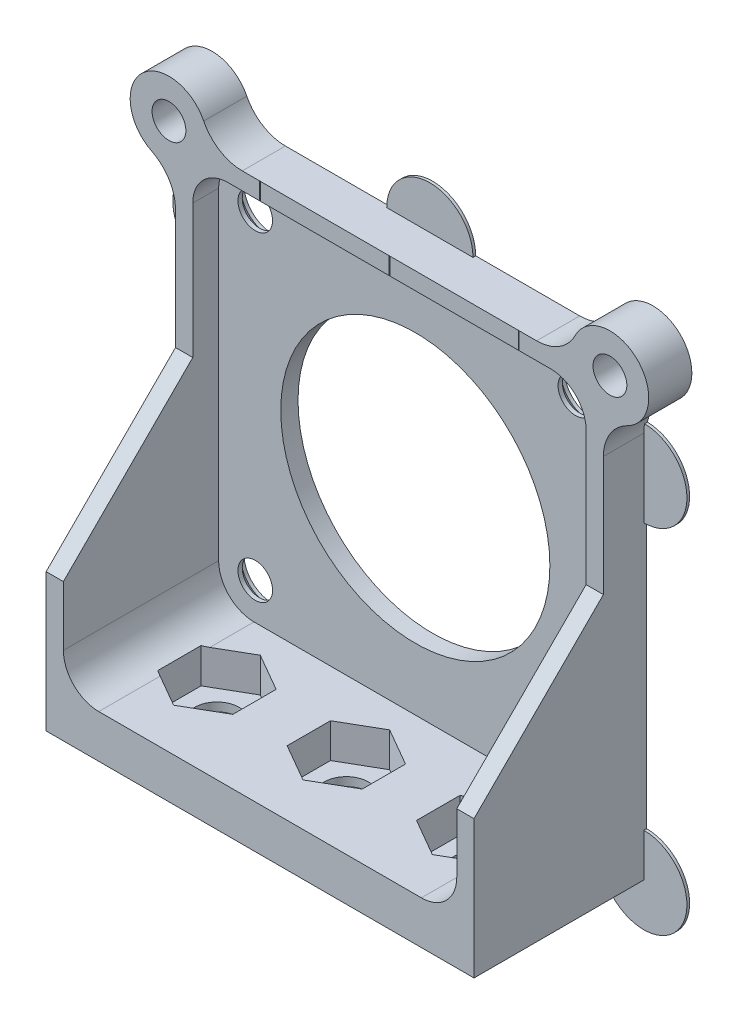
SolidWorks part; units mm, degrees
ref_plane "Front Plane" through (0, 0, 0) normal (0, 0, 1) x (1, 0, 0)
ref_plane "Top Plane" through (0, 0, 0) normal (0, 1, 0) x (1, 0, 0)
ref_plane "Right Plane" through (0, 0, 0) normal (1, 0, 0) x (0, 0, -1)
sketch "Sketch2" plane through (0, 0, 0) normal (0, 0, 1) x (1, 0, 0)
  line L12 (-28.2, 23.755) -> (-28.2, -23.755)
  line L13 (-23.755, -28.2) -> (23.755, -28.2)
  line L14 (28.2, -23.755) -> (28.2, 23.755)
  line L15 (23.755, 28.2) -> (-23.755, 28.2)
  circle A0 centre (0, 0) radius 19.05
  circle A1 centre (-23.57, 23.57) radius 2.55
  circle A2 centre (23.57, 23.57) radius 2.55
  circle A3 centre (23.57, -23.57) radius 2.55
  circle A4 centre (-23.57, -23.57) radius 2.55
  arc A12 (-23.755, 28.2) -> (-28.2, 23.755) centre (-23.755, 23.755) ccw
  arc A13 (-28.2, -23.755) -> (-23.755, -28.2) centre (-23.755, -23.755) ccw
  arc A14 (23.755, -28.2) -> (28.2, -23.755) centre (23.755, -23.755) ccw
  arc A15 (28.2, 23.755) -> (23.755, 28.2) centre (23.755, 23.755) ccw
sketch "Sketch3" plane through (0, 0, 0) normal (0, 0, 1) x (1, 0, 0)
  line L9 (23.755, 31.502) -> (-23.755, 31.502)
  line L10 (-31.502, 23.755) -> (-31.502, -23.755)
  line L11 (-23.755, -31.502) -> (23.755, -31.502)
  line L12 (31.502, -23.755) -> (31.502, 23.755)
  line L13 (23.755, 28.962) -> (-23.755, 28.962)
  line L14 (-28.962, 23.755) -> (-28.962, -23.755)
  line L15 (-23.755, -28.962) -> (23.755, -28.962)
  line L16 (28.962, -23.755) -> (28.962, 23.755)
  line L17 (23.755, 28.962) -> (-23.755, 28.962) construction
  line L18 (-28.962, 23.755) -> (-28.962, -23.755) construction
  line L19 (-23.755, -28.962) -> (23.755, -28.962) construction
  line L20 (28.962, -23.755) -> (28.962, 23.755) construction
  circle A0 centre (0, 0) radius 19.812
  circle A1 centre (23.57, 23.57) radius 2.55
  circle A2 centre (-23.57, 23.57) radius 2.55
  circle A3 centre (-23.57, -23.57) radius 2.55
  circle A4 centre (23.57, -23.57) radius 2.55
  circle A9 centre (0, 0) radius 19.05 construction
  arc A10 (-23.755, 31.502) -> (-31.502, 23.755) centre (-23.755, 23.755) ccw
  arc A11 (-31.502, -23.755) -> (-23.755, -31.502) centre (-23.755, -23.755) ccw
  arc A12 (23.755, -31.502) -> (31.502, -23.755) centre (23.755, -23.755) ccw
  arc A13 (31.502, 23.755) -> (23.755, 31.502) centre (23.755, 23.755) ccw
  arc A14 (-23.755, 28.962) -> (-28.962, 23.755) centre (-23.755, 23.755) ccw
  arc A15 (-28.962, -23.755) -> (-23.755, -28.962) centre (-23.755, -23.755) ccw
  arc A16 (23.755, -28.962) -> (28.962, -23.755) centre (23.755, -23.755) ccw
  arc A17 (28.962, 23.755) -> (23.755, 28.962) centre (23.755, 23.755) ccw
  arc A18 (-23.755, 28.962) -> (-28.962, 23.755) centre (-23.755, 23.755) ccw construction
  arc A19 (-28.962, -23.755) -> (-23.755, -28.962) centre (-23.755, -23.755) ccw construction
  arc A20 (23.755, -28.962) -> (28.962, -23.755) centre (23.755, -23.755) ccw construction
  arc A21 (28.962, 23.755) -> (23.755, 28.962) centre (23.755, 23.755) ccw construction
  dimension "D6" = 0.762
  dimension "D1" = 0.762
  dimension "D2" = 2.54
extrude "Boss-Extrude1" add sketch "Sketch3" along normal blind 2.54
sketch "Sketch16" plane through (0, 0, 2.54) normal (0, 0, 1) x (1, 0, 0)
  line L8 (23.755, 28.962) -> (-23.755, 28.962)
  line L9 (-28.962, 23.755) -> (-28.962, -23.755)
  line L10 (23.755, 31.502) -> (-23.755, 31.502)
  line L11 (-31.502, 23.755) -> (-31.502, -23.755)
  line L12 (-23.755, -31.502) -> (23.755, -31.502)
  line L13 (31.502, -23.755) -> (31.502, 23.755)
  line L14 (23.755, 31.502) -> (-23.755, 31.502)
  line L15 (-31.502, 23.755) -> (-31.502, -23.755)
  line L16 (-23.755, -31.502) -> (23.755, -31.502)
  line L17 (31.502, -23.755) -> (31.502, 23.755)
  line L18 (-23.755, -28.962) -> (23.755, -28.962)
  line L23 (28.962, -23.755) -> (28.962, 23.755)
  line L24 (23.755, 28.962) -> (-23.755, 28.962)
  line L25 (-28.962, 23.755) -> (-28.962, -23.755)
  line L26 (-23.755, -28.962) -> (23.755, -28.962)
  line L27 (28.962, -23.755) -> (28.962, 23.755)
  arc A8 (28.962, 23.755) -> (23.755, 28.962) centre (23.755, 23.755) ccw
  arc A9 (31.502, 23.755) -> (23.755, 31.502) centre (23.755, 23.755) ccw
  arc A10 (-23.755, 31.502) -> (-31.502, 23.755) centre (-23.755, 23.755) ccw
  arc A11 (-31.502, -23.755) -> (-23.755, -31.502) centre (-23.755, -23.755) ccw
  arc A12 (23.755, -31.502) -> (31.502, -23.755) centre (23.755, -23.755) ccw
  arc A13 (31.502, 23.755) -> (23.755, 31.502) centre (23.755, 23.755) ccw
  arc A14 (-23.755, 31.502) -> (-31.502, 23.755) centre (-23.755, 23.755) ccw
  arc A15 (-31.502, -23.755) -> (-23.755, -31.502) centre (-23.755, -23.755) ccw
  arc A16 (23.755, -31.502) -> (31.502, -23.755) centre (23.755, -23.755) ccw
  arc A21 (-23.755, 28.962) -> (-28.962, 23.755) centre (-23.755, 23.755) ccw
  arc A22 (-28.962, -23.755) -> (-23.755, -28.962) centre (-23.755, -23.755) ccw
  arc A23 (23.755, -28.962) -> (28.962, -23.755) centre (23.755, -23.755) ccw
  arc A24 (28.962, 23.755) -> (23.755, 28.962) centre (23.755, 23.755) ccw
  arc A25 (-23.755, 28.962) -> (-28.962, 23.755) centre (-23.755, 23.755) ccw
  arc A26 (-28.962, -23.755) -> (-23.755, -28.962) centre (-23.755, -23.755) ccw
  arc A27 (23.755, -28.962) -> (28.962, -23.755) centre (23.755, -23.755) ccw
  dimension "D1" = 0
  dimension "D2" = 2.54
extrude "Boss-Extrude6" add sketch "Sketch16" along normal blind 3.81
sketch "Sketch17" plane through (0, 0, 2.54) normal (0, 0, 1) x (1, 0, 0)
  line L0 (-31.502, 23.755) -> (-31.502, -23.755) construction
  line L1 (31.502, -35.312) -> (-31.502, -35.312)
  line L2 (31.502, -35.312) -> (31.502, -16.262)
  line L3 (31.502, -16.262) -> (28.962, -16.262)
  line L4 (-31.502, -35.312) -> (-31.502, -16.262)
  line L12 (-28.962, -16.262) -> (-31.502, -16.262)
  line L13 (-28.962, 23.755) -> (-28.962, -23.755) construction
  line L14 (28.962, -23.755) -> (28.962, 23.755) construction
  line L15 (31.502, -23.755) -> (31.502, 23.755) construction
  line L16 (-23.755, -28.962) -> (23.755, -28.962) construction
  dimension "D1" = 6.35
  dimension "D2" = 19.05
extrude "Boss-Extrude10" add sketch "Sketch17" along normal blind 22.86 and the other way blind 2.54
chamfer "Chamfer1" distance 20.32 angle 45 2 edges at (30.232, -16.262, 6.35) (-30.232, -16.262, 6.35)
sketch "Sketch18" plane through (0, -28.962, 0) normal (0, -1, 0) x (1, 0, 0)
  line L1 (0, 0) -> (0, 25.4) construction
  line L3 (19.05, 0) -> (-19.05, 0) construction
  line L4 (0, 19.0791) -> (-5.5245, 15.8896)
  line L5 (-5.5245, 15.8896) -> (-5.5245, 9.5104)
  line L6 (-5.5245, 9.5104) -> (0, 6.3209)
  line L7 (0, 6.3209) -> (5.5245, 9.5104)
  line L8 (5.5245, 9.5104) -> (5.5245, 15.8896)
  line L9 (5.5245, 15.8896) -> (0, 19.0791)
  line L13 (-31.502, 12.7) -> (31.502, 12.7) construction
  line L14 (-31.502, 25.4) -> (-31.502, 6.35) construction
  line L15 (31.502, 6.35) -> (31.502, 25.4) construction
  line L16 (-9.525, 25.4) -> (-9.525, 0) construction
  line L17 (12.452, 12.7) -> (-50.552, 12.7) construction
  line L18 (-19.05, 0) -> (-19.05, 25.4) construction
  line L19 (-24.5745, 15.8896) -> (-19.05, 19.0791)
  line L20 (-24.5745, 9.5104) -> (-24.5745, 15.8896)
  line L21 (-19.05, 6.3209) -> (-24.5745, 9.5104)
  line L22 (-13.5255, 9.5104) -> (-19.05, 6.3209)
  line L23 (-13.5255, 15.8896) -> (-13.5255, 9.5104)
  line L24 (-19.05, 19.0791) -> (-13.5255, 15.8896)
  line L25 (19.05, 0) -> (19.05, 25.4) construction
  line L26 (-12.452, 12.7) -> (50.552, 12.7) construction
  line L27 (19.05, 19.0791) -> (13.5255, 15.8896)
  line L28 (13.5255, 15.8896) -> (13.5255, 9.5104)
  line L29 (13.5255, 9.5104) -> (19.05, 6.3209)
  line L30 (19.05, 6.3209) -> (24.5745, 9.5104)
  line L31 (24.5745, 9.5104) -> (24.5745, 15.8896)
  line L32 (24.5745, 15.8896) -> (19.05, 19.0791)
  line L33 (-23.755, 25.4) -> (23.755, 25.4) construction
  circle A0 centre (0, 12.7) radius 5.5245 construction
  circle A1 centre (-19.05, 12.7) radius 5.5245 construction
  circle A2 centre (19.05, 12.7) radius 5.5245 construction
  dimension "D1" = 11.049
  dimension "D2" = 9.525
extrude "Cut-Extrude2" cut sketch "Sketch18" along normal blind 5.08 and the other way through all
hole_wizard "1/4 Clearance Hole1" positions "Sketch20" profile "Sketch19" hole size "1/4" standard "ANSI Inch" end condition through all
sketch "Sketch20" plane through (0, -34.042, 0) normal (0, 1, 0) x (1, 0, 0)
  line L4 (-24.5745, -15.8896) -> (-13.5255, -9.5104) construction
  line L5 (-19.05, -6.3209) -> (-13.5255, -9.5104) construction
  line L6 (-13.5255, -9.5104) -> (-13.5255, -15.8896) construction
  line L8 (-5.5245, -15.8896) -> (5.5245, -9.5104) construction
  line L10 (13.5255, -15.8896) -> (24.5745, -9.5104) construction
  line L12 (13.5255, -15.8896) -> (19.05, -19.0791) construction
  line L13 (19.05, -19.0791) -> (13.5255, -15.8896) construction
  point P22 (-19.05, -12.7)
  point P24 (0, -12.7)
  point P26 (19.05, -12.7)
sketch "Sketch19" plane through (-19.05, -34.042, 12.7) normal (1, 0, 0) x (0, 0, 1)
  line L0 (0, 0) -> (0, 1.27)
  line L1 (0, 1.27) -> (3.2639, 1.27)
  line L2 (3.2639, 1.27) -> (3.2639, 0)
  line L5 (3.2639, 0) -> (0, 0)
  line L11 (0, -6.35) -> (0, 107.95) construction
  dimension "Thru Hole Dia." = 6.5278
  dimension "Thru Hole Depth" = 1.27
sketch "Sketch22" plane through (0, 0, 0) normal (0, 0, -1) x (-1, 0, 0)
  line L0 (-29.233, 29.233) -> (23.57, -23.57) construction
  line L3 (-29.233, 29.233) -> (-43.8337, 43.8337) construction
  arc A0 (-23.755, 31.502) -> (-31.502, 23.755) centre (-23.755, 23.755) ccw construction
  circle A1 centre (-32.4658, 32.4658) radius 5.715
  circle A2 centre (-32.4658, 32.4658) radius 2.413
  arc A3 (-23.755, 28.2) -> (-28.2, 23.755) centre (-23.755, 23.755) ccw construction
  point P12 (-26.8981, 26.8981)
  arc M3 (-23.755, 31.502) -> (-31.502, 23.755) centre (-23.755, 23.755) ccw
  dimension "D1" = 11.43
  dimension "D2" = 4.826
  dimension "D3" = 7.874
extrude "Boss-Extrude18" add sketch "Sketch22" against normal up to surface (6.35 mm away) contours A1 A2 M3 region at (26.974, 31.6417, 0) up to face at (26.1652, 22.4046, 6.35)
mirror "Mirror3" about plane through (0, 0, 0) normal (1, 0, 0) of "Boss-Extrude18"
fillet "Fillet1" radius 6.35 4 edges at (27.0026, 30.7884, 3.175) (30.7884, 27.0026, 3.175) (-30.7884, 27.0026, 3.175) (-27.0026, 30.7884, 3.175)
hole_wizard "CSK for  Flat Head Machine Screw (100)1" positions "Sketch24" profile "Sketch23" countersink size "#10" standard "ANSI Inch" end condition through all
sketch "Sketch24" plane through (0, 0, 0) normal (0, 0, -1) x (-1, 0, 0)
  point P0 (-23.57, 23.57)
  point P3 (23.57, 23.57)
  point P6 (23.57, -23.57)
  point P9 (-23.57, -23.57)
sketch "Sketch23" plane through (23.57, 23.57, 0) normal (1, 0, 0) x (0, 1, 0)
  line L0 (0, 0) -> (0, 25.4)
  line L1 (0, 25.4) -> (2.4892, 25.4)
  line L2 (2.4892, 25.4) -> (2.4892, 1.9573)
  line L3 (2.4892, 1.9573) -> (4.2164, 0.508)
  line L4 (4.2164, 0.508) -> (4.2164, 0)
  line L6 (4.2164, 0) -> (0, 0)
  line L7 (-2.4892, 1.9573) -> (-4.2164, 0.508) construction
  line L11 (0, -6.35) -> (0, 107.95) construction
  dimension "Thru Hole Dia." = 4.9784
  dimension "Thru Hole Depth" = 25.4
  dimension "C'Sink Dia." = 8.4328
  dimension "C'Sink Angle" = 100
  dimension "Head Clearance" = 0.508
hole_wizard "#10 Clearance Hole1" positions "Sketch26" profile "Sketch25" hole size "#10" standard "ANSI Inch" end condition through all
sketch "Sketch26" plane through (0, 0, 0) normal (0, 0, -1) x (-1, 0, 0)
  point P0 (-32.4658, 32.4658)
  point P3 (32.4658, 32.4658)
sketch "Sketch25" plane through (32.4658, 32.4658, 0) normal (1, 0, 0) x (0, 1, 0)
  line L0 (0, 0) -> (0, 25.4)
  line L1 (0, 25.4) -> (2.4892, 25.4)
  line L2 (2.4892, 25.4) -> (2.4892, 0)
  line L5 (2.4892, 0) -> (0, 0)
  line L11 (0, -6.35) -> (0, 107.95) construction
  dimension "Thru Hole Dia." = 4.9784
  dimension "Thru Hole Depth" = 25.4
sketch "Sketch6" plane through (0, -30.232, 0) normal (0, 0, -1) x (-1, 0, 0)
  line L0 (0, -5.08) -> (0, 46.8212) construction
  line L1 (-31.502, -5.08) -> (31.502, -5.08) construction
  line L2 (31.502, 51.9018) -> (31.502, -5.08) construction
  line L3 (0, 20.8706) -> (31.502, 20.8706) construction
  line L4 (31.502, 15.24) -> (31.502, 34.29) construction
  line L5 (-21.6698, 61.734) -> (21.6698, 61.734) construction
  circle A0 centre (31.502, -5.08) radius 6.35
  circle A1 centre (-31.502, -5.08) radius 6.35
  circle A2 centre (-31.502, 46.8212) radius 6.35
  circle A3 centre (31.502, 46.8212) radius 6.35
  circle A4 centre (23.57, 53.802) radius 4.2164 construction
  circle A5 centre (0, 61.734) radius 6.35
  dimension "D1" = 12.7
  dimension "D2" = 12.7
extrude "Tabs" add sketch "Sketch6" against normal blind 0.4
equation "\"wall_thickness\"=0.15"
equation "\"head_depth\"=0.18"
